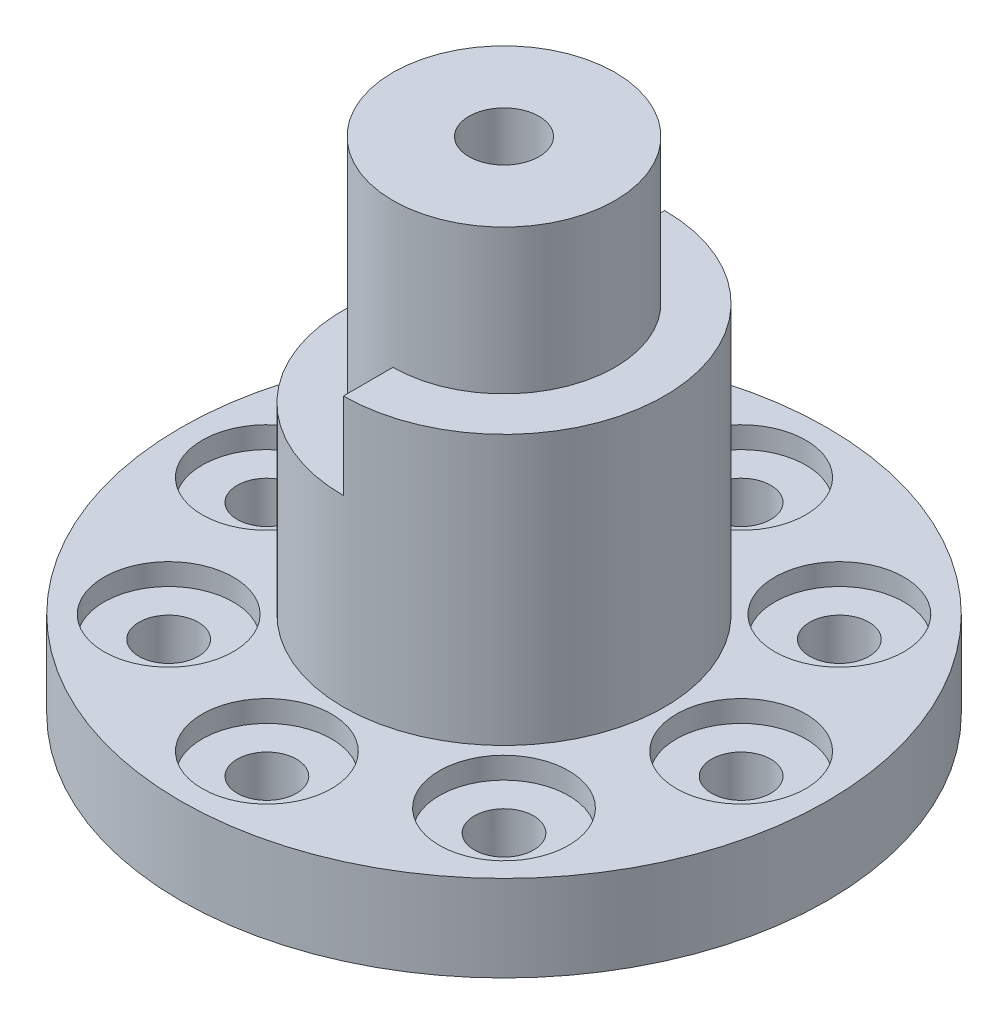
SolidWorks part; units mm, degrees
ref_plane "Front Plane" through (0, 0, 0) normal (0, 0, 1) x (1, 0, 0)
ref_plane "Top Plane" through (0, 0, 0) normal (0, 1, 0) x (1, 0, 0)
ref_plane "Right Plane" through (0, 0, 0) normal (1, 0, 0) x (0, 0, -1)
sketch "Sketch1" plane through (0, 0, 0) normal (0, 1, 0) x (1, 0, 0)
  circle A0 centre (0, 0) radius 7.5
  circle A1 centre (0, 0) radius 5.15
  dimension "D1" = 15
  dimension "D2" = 10.3
extrude "Boss-Extrude1" add sketch "Sketch1" along normal blind 5 contours A1 | A0 A1 region at (-7.2879, 0, 0) region at (0, 0, 0)
extrude "Boss-Extrude2" add sketch "Sketch1<3>" along normal blind 15.7 contours A1 region at (0, 0, 0)
sketch "Sketch1<3>" plane through (0, 0, 0) normal (0, 1, 0) x (1, 0, 0) same geometry as "Sketch1"
sketch "Sketch2" plane through (0, 5, 0) normal (0, 1, 0) x (1, 0, 0)
  line L0 (0, 7.5) -> (0, -7.5)
  circle A0 centre (0, 0) radius 7.5
  circle M2 centre (0, 0) radius 5.15
  circle M3 centre (0, 0) radius 7.5
extrude "Boss-Extrude3" add sketch "Sketch2" along normal blind 4 contours L0 M3 M2 region at (5.1847, 5, -5.1847)
sketch "Sketch3" plane through (0, 0, 0) normal (0, -1, 0) x (1, 0, 0)
  circle A0 centre (0, 0) radius 1.625
  dimension "D1" = 3.25
extrude "Cut-Extrude1" cut sketch "Sketch3" against normal blind 37
sketch "Sketch4" plane through (0, 0, 0) normal (0, -1, 0) x (1, 0, 0)
  circle A0 centre (0, 0) radius 3.5
  dimension "D1" = 7
extrude "Cut-Extrude2" cut sketch "Sketch4" against normal blind 10.7
sketch "Sketch5" plane through (0, 0, 0) normal (0, -1, 0) x (1, 0, 0)
  circle A0 centre (0, 0) radius 3.5
  circle A1 centre (0, 0) radius 7.5
extrude "Boss-Extrude4" add sketch "Sketch5" along normal blind 3.5
sketch "Sketch6" plane through (0, -3.5, 0) normal (0, -1, 0) x (1, 0, 0)
  circle A0 centre (0, 0) radius 3.5
  circle A1 centre (0, 0) radius 11
  circle A2 centre (-11, 0) radius 1.375
  circle A3 centre (-7.7782, 7.7782) radius 1.375
  circle A4 centre (0, 11) radius 1.375
  circle A5 centre (7.7782, 7.7782) radius 1.375
  circle A6 centre (11, 0) radius 1.375
  circle A7 centre (7.7782, -7.7782) radius 1.375
  circle A8 centre (0, -11) radius 1.375
  circle A9 centre (-7.7782, -7.7782) radius 1.375
  circle A10 centre (0, 0) radius 15
  point P22 (0, 0)
  circle M1 centre (0, 0) radius 7.5
  circle M2 centre (0, 0) radius 3.5
  dimension "D1" = 22
  dimension "D2" = 2.75
  dimension "D4" = 30
  dimension "D3" = 8
extrude "Boss-Extrude5" add sketch "Sketch6" along normal blind 4 contours A9 A1 A8 A7 A6 A5 A4 A3 A2 M1 | M1 M2 | A10 A9 A1 A2 A3 A4 A5 A6 A7 A8 region at (9.3163, -3.5, 0) region at (-14.5757, -3.5, 0) region at (-7.2879, -3.5, 0)
sketch "Sketch7" plane through (0, -3.5, 0) normal (0, 1, 0) x (1, 0, 0)
  circle A0 centre (-11, 0) radius 3
  circle A1 centre (-7.7782, 7.7782) radius 3
  circle A2 centre (0, 11) radius 3
  circle A3 centre (7.7782, 7.7782) radius 3
  circle A4 centre (11, 0) radius 3
  circle A5 centre (7.7782, -7.7782) radius 3
  circle A6 centre (0, -11) radius 3
  circle A7 centre (-7.7782, -7.7782) radius 3
  point P19 (0, 0)
  dimension "D1" = 6
  dimension "D2" = 8
extrude "Cut-Extrude3" cut sketch "Sketch7" against normal blind 1
sketch "Sketch8" plane through (0, 9, 0) normal (0, 1, 0) x (1, 0, 0)
  circle A0 centre (0, 0) radius 7.5
  circle A1 centre (0, 0) radius 7.45
  dimension "D1" = 14.9
extrude "Cut-Extrude4" cut sketch "Sketch8" against normal blind 12.5
